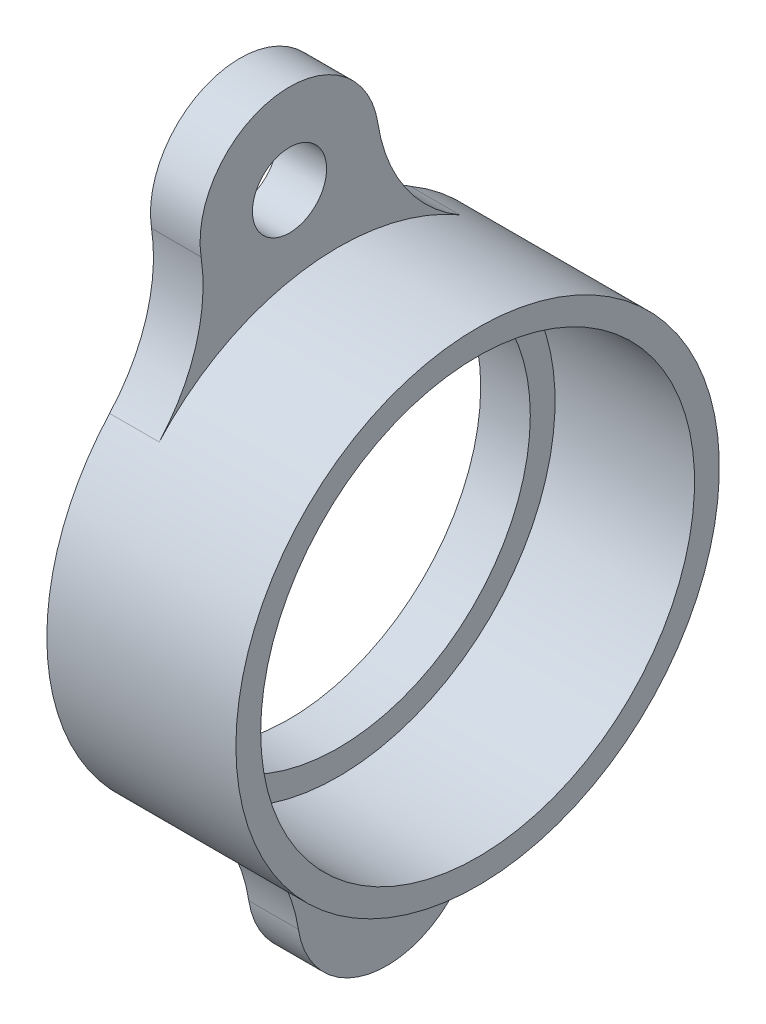
SolidWorks part; units mm, degrees
ref_plane "Front Plane" through (0, 0, 0) normal (0, 0, 1) x (1, 0, 0)
ref_plane "Top Plane" through (0, 0, 0) normal (0, 1, 0) x (1, 0, 0)
ref_plane "Right Plane" through (0, 0, 0) normal (1, 0, 0) x (0, 0, -1)
sketch "Sketch1" plane through (0, 0, 0) normal (0, 0, 1) x (1, 0, 0)
  line L0 (25.4, 12.3825) -> (32.5437, 12.3825)
  line L1 (32.5437, 12.3825) -> (32.5437, 11.1125)
  line L2 (32.5437, 11.1125) -> (25.4, 11.1125)
  line L4 (25.4, 11.1125) -> (25.4, 12.3825)
  line L5 (0, 0) -> (40.0174, 0) construction
  dimension "D1" = 1.27
  dimension "D2" = 7.1437
revolve "Revolve1" add sketch "Sketch1" angle 360 about L5
sketch "Sketch2" plane through (25.4, 0, 0) normal (1, 0, 0) x (0, 0, -1)
  line L0 (3.6746, -23.8319) -> (-3.6746, 23.8319) construction
  line L1 (-7.0209, 15.4619) -> (2.0375, 16.8586) construction
  line L2 (-11.4922, -1.772) -> (11.4922, 1.772) construction
  line L4 (-4.1515, 11.8887) -> (0.3777, 12.5871) construction
  line L5 (0.3777, 12.5871) -> (2.0375, 16.8586) construction
  line L6 (2.0375, 16.8586) -> (-0.8319, 20.4319) construction
  line L7 (-0.8319, 20.4319) -> (-5.3611, 19.7335) construction
  line L8 (-5.3611, 19.7335) -> (-7.0209, 15.4619) construction
  line L9 (-7.0209, 15.4619) -> (-4.1515, 11.8887) construction
  arc A0 (-9.1674, 8.3237) -> (-6.2344, -10.6985) centre (0, 0) ccw
  circle A1 centre (0, 0) radius 12.3825 construction
  arc A7 (2.0375, 16.8586) -> (-7.0209, 15.4619) centre (-2.4917, 16.1603) ccw
  arc A8 (-9.1674, 8.3237) -> (-7.0209, 15.4619) centre (-15.5764, 14.1428) ccw
  arc A9 (2.0375, 16.8586) -> (6.2344, 10.6985) centre (10.5929, 18.1778) ccw
  circle A10 centre (0, 0) radius 9.8425
  circle A11 centre (0, 0) radius 11.1125 construction
  arc A12 (7.0209, -15.4619) -> (9.1674, -8.3237) centre (15.5764, -14.1428) cw
  arc A14 (7.0209, -15.4619) -> (-2.0375, -16.8586) centre (2.4917, -16.1603) cw
  arc A15 (-6.2344, -10.6985) -> (-2.0375, -16.8586) centre (-10.5929, -18.1778) cw
  arc A16 (9.1674, -8.3237) -> (6.2344, 10.6985) centre (0, 0) ccw
  circle A17 centre (-2.4917, 16.1603) radius 3.9688 construction
  arc A18 (1.5529, 20.0011) -> (-7.5055, 18.6044) centre (-2.9763, 19.3027) ccw construction
  arc A19 (-1.5529, -20.0011) -> (7.5055, -18.6044) centre (2.9763, -19.3027) ccw construction
  dimension "D1" = 1.27
  dimension "D3" = 7.9375
extrude "Boss-Extrude1" add sketch "Sketch2" against normal blind 2.54
hole_wizard "#6 Clearance Hole1" positions "Sketch3" profile "Sketch5" hole size "#6" standard "ANSI Inch" end condition up to next
sketch "Sketch3" plane through (22.86, 0, 0) normal (-1, 0, 0) x (0, 0, 1)
  point P0 (2.4917, 16.1603)
  point P3 (-2.4917, -16.1603)
sketch "Sketch5" plane through (22.86, 16.1603, 2.4917) normal (0, 1, 0) x (0, 0, 1)
  line L0 (0, 0) -> (0, 2.54)
  line L1 (0, 2.54) -> (1.8986, 2.54)
  line L2 (1.8986, 2.54) -> (1.8986, 0)
  line L5 (1.8986, 0) -> (0, 0)
  line L11 (0, -6.35) -> (0, 107.95) construction
  dimension "Thru Hole Dia." = 3.7973
  dimension "Thru Hole Depth" = 2.54
